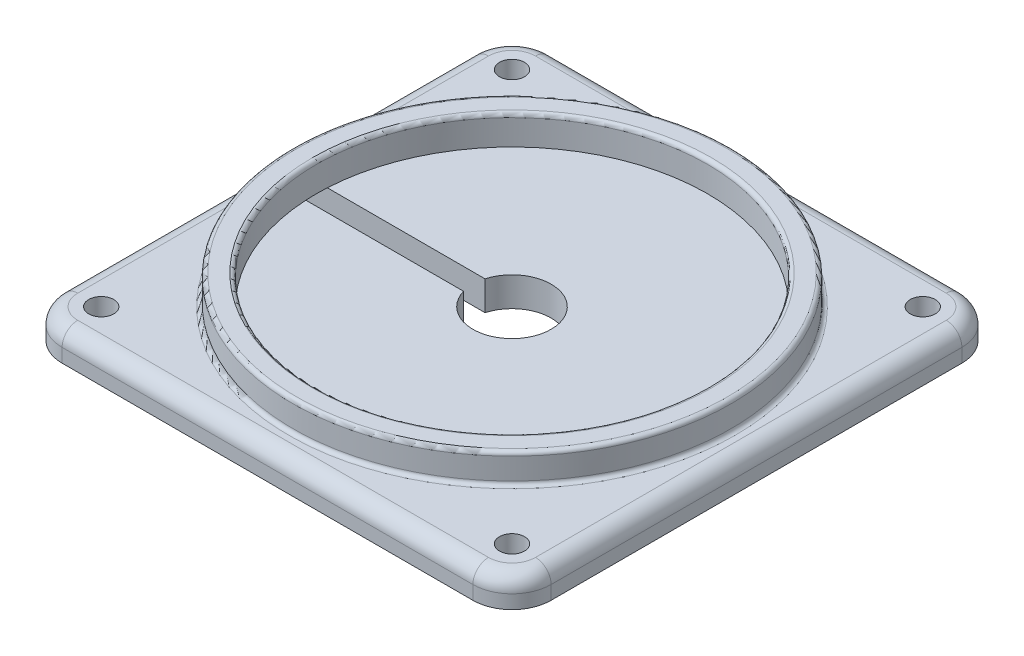
SolidWorks part; units mm, degrees
ref_plane "Front" through (0, 0, 0) normal (0, 0, 1) x (1, 0, 0)
ref_plane "Top" through (0, 0, 0) normal (0, 1, 0) x (1, 0, 0)
ref_plane "Right" through (0, 0, 0) normal (1, 0, 0) x (0, 0, -1)
sketch "草图1" plane through (0, 0, 0) normal (0, 1, 0) x (1, 0, 0)
  line L1 (-62.5, -62.5) -> (62.5, -62.5)
  line L2 (-62.5, -62.5) -> (-62.5, 62.5)
  line L3 (-62.5, 62.5) -> (62.5, 62.5)
  line L4 (62.5, -62.5) -> (62.5, 62.5)
  line L5 (-62.5, -62.5) -> (62.5, 62.5) construction
  line L6 (-62.5, 62.5) -> (62.5, -62.5) construction
  point P0 (0, 0)
  dimension "D1" = 125
  dimension "D2" = 125
extrude "凸台-拉伸1" add sketch "草图1" along normal blind 15
sketch "草图2" plane through (0, 15, 0) normal (0, 1, 0) x (1, 0, 0)
  circle A0 centre (0, 0) radius 50
  dimension "D1" = 100
extrude "切除-拉伸1" cut sketch "草图2" against normal blind 7.5
sketch "草图3" plane through (0, 7.5, 0) normal (0, 1, 0) x (1, 0, 0)
  circle A0 centre (0, 0) radius 10
  dimension "D1" = 20
extrude "切除-拉伸2" cut sketch "草图3" against normal through all
sketch "草图4" plane through (0, 15, 0) normal (0, 1, 0) x (1, 0, 0)
  line L0 (-102.8194, 0) -> (120.576, 0) construction
  line L1 (0, 64.3467) -> (0, -64.6849) construction
  line L2 (-62.5, 62.5) -> (62.5, -62.5) construction
  line L3 (62.5, 62.5) -> (-62.5, 62.5) construction
  circle A0 centre (-52.5, 52.5) radius 3.2
  circle A1 centre (-52.5, -52.5) radius 3.2
  circle A2 centre (52.5, -52.5) radius 3.2
  circle A3 centre (52.5, 52.5) radius 3.2
  dimension "D1" = 6.4
  dimension "D2" = 10
extrude "切除-拉伸3" cut sketch "草图4" against normal through all
sketch "草图6" plane through (0, 15, 0) normal (0, 1, 0) x (1, 0, 0)
  line L1 (-62.5, -62.5) -> (62.5, -62.5)
  line L2 (-62.5, -62.5) -> (-62.5, 62.5)
  line L3 (-62.5, 62.5) -> (62.5, 62.5)
  line L4 (62.5, -62.5) -> (62.5, 62.5)
  line L5 (-62.5, -62.5) -> (62.5, 62.5) construction
  line L6 (-62.5, 62.5) -> (62.5, -62.5) construction
  circle A0 centre (0, 0) radius 56
  point P0 (0, 0)
  dimension "D1" = 112
extrude "切除-拉伸4" cut sketch "草图6" against normal blind 7.5
sketch "草图7" plane through (-62.5, 0, 0) normal (-1, 0, 0) x (0, 0, 1)
  line L0 (-62.5, 7.5) -> (62.5, 7.5) construction
  line L1 (-2.7255, 0) -> (2.7745, 0)
  line L2 (-2.7255, 0) -> (-2.7255, 7.5)
  line L3 (-2.7255, 7.5) -> (2.7745, 7.5)
  line L4 (2.7745, 0) -> (2.7745, 7.5)
  line L5 (-2.7255, 0) -> (2.7745, 7.5) construction
  line L6 (-2.7255, 7.5) -> (2.7745, 0) construction
  line L7 (-62.5, 0) -> (62.5, 0) construction
  point P0 (0.0245, 3.75)
  dimension "D1" = 5.5
extrude "切除-拉伸5" cut sketch "草图7" against normal up to next
fillet "圆角1" radius 4 5 edges at (0, 7.5, 62.5) (62.5, 7.5, 0) (0, 7.5, -62.5) (-62.5, 7.5, 32.6373) (-62.5, 7.5, -32.6127)
fillet "圆角2" radius 10 8 edges at (-62.5, 1.75, -62.5) (-62.5, 1.75, 62.5) (62.5, 1.75, -62.5) (62.5, 1.75, 62.5) (61.3284, 6.3284, 61.3284) (61.3284, 6.3284, -61.3284) (-61.3284, 6.3284, -61.3284) (-61.3284, 6.3284, 61.3284)
fillet "圆角3" radius 1 2 edges at (0, 15, 56) (0, 15, 50)
fillet "圆角4" radius 1 1 edges at (56, 7.5, -0.0246)
